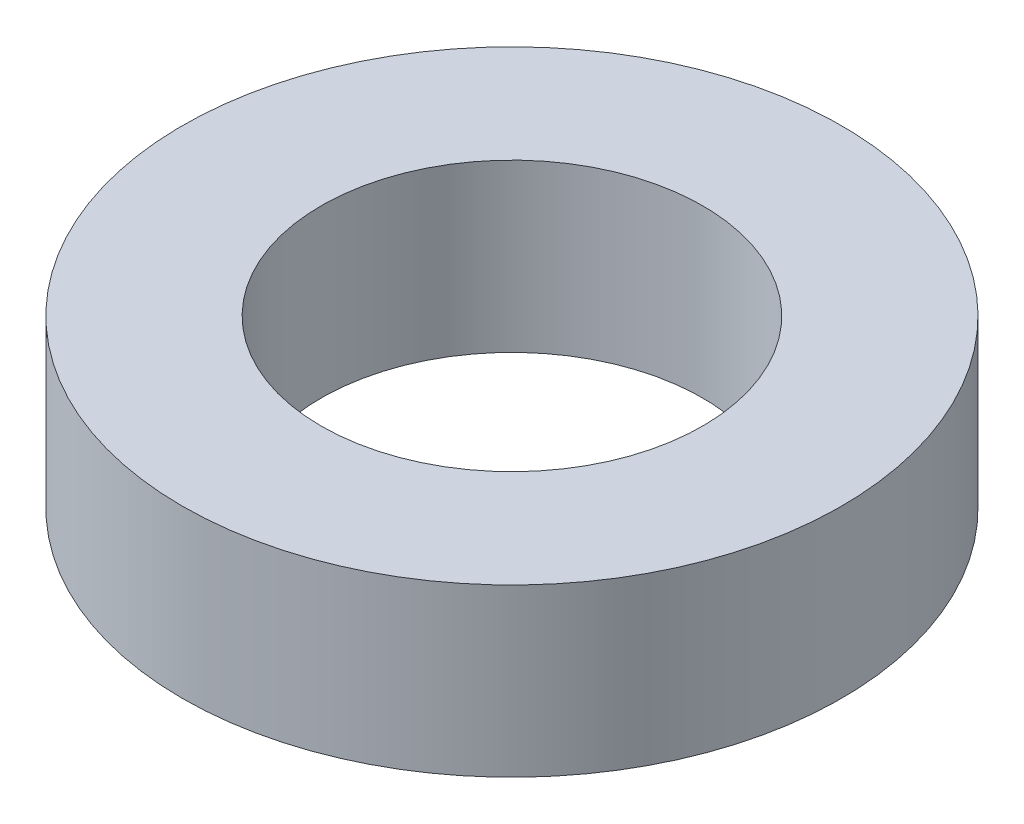
SolidWorks part; units mm, degrees
ref_plane "Front Plane" through (0, 0, 0) normal (0, 0, 1) x (1, 0, 0)
ref_plane "Top Plane" through (0, 0, 0) normal (0, 1, 0) x (1, 0, 0)
ref_plane "Right Plane" through (0, 0, 0) normal (1, 0, 0) x (0, 0, -1)
sketch "Sketch1" plane through (0, 0, 0) normal (0, 1, 0) x (1, 0, 0)
  circle A0 centre (0, 0) radius 47.5
  dimension "FLANGE_OD" = 95
extrude "Boss-Extrude1" add sketch "Sketch1" along normal blind 24
sketch "Sketch2" plane through (0, 0, 0) normal (0, 1, 0) x (1, 0, 0)
  circle A0 centre (0, 0) radius 27.5
  dimension "BORE_D" = 55
extrude "Cut-Extrude1" cut sketch "Sketch2" along normal through all
sketch "Sketch3" plane through (0, 24, 0) normal (0, 1, 0) x (1, 0, 0)
  circle A0 centre (0, 0) radius 17.6402 construction
  circle A1 centre (-17.6402, 0) radius 2.1581
  dimension "BOLT_D" = 4.3162
  dimension "BOLT_PCD" = 35.2804
extrude "Cut-Extrude2" cut sketch "Sketch3" against normal blind 15.8376 rebuild error yes
pattern_circular "CirPattern1" count 4 over 360 rebuild error yes
